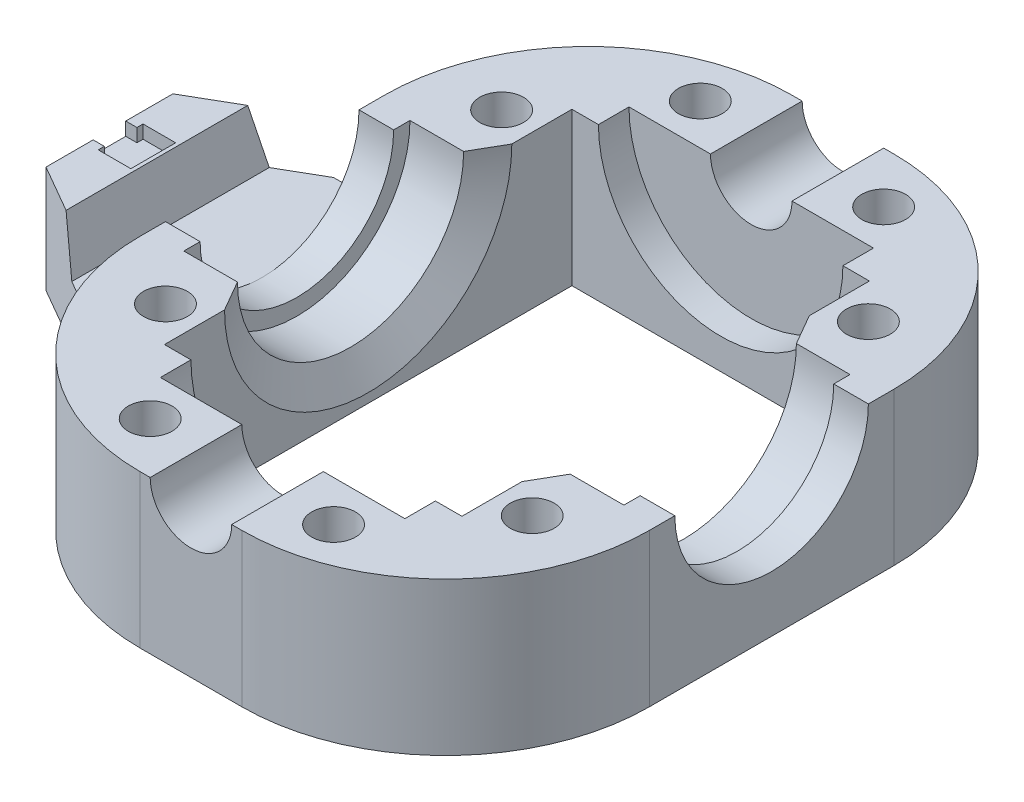
SolidWorks part; units mm, degrees
ref_plane "Спереди" through (0, 0, 0) normal (0, 0, 1) x (1, 0, 0)
ref_plane "Сверху" through (0, 0, 0) normal (0, 1, 0) x (1, 0, 0)
ref_plane "Справа" through (0, 0, 0) normal (1, 0, 0) x (0, 0, -1)
sketch "Sketch1" plane through (0, 0, 0) normal (0, 1, 0) x (1, 0, 0)
  line L1 (25, -32) -> (-25, -32)
  line L2 (25, -32) -> (25, 32)
  line L3 (25, 32) -> (-25, 32)
  line L4 (-25, -32) -> (-25, 32)
  line L5 (25, -32) -> (-25, 32) construction
  line L6 (25, 32) -> (-25, -32) construction
  line L7 (14.6, -20) -> (-14.6, -20)
  line L8 (14.6, -20) -> (14.6, 20)
  line L9 (14.6, 20) -> (-14.6, 20)
  line L10 (-14.6, -20) -> (-14.6, 20)
  line L11 (14.6, -20) -> (-14.6, 20) construction
  line L12 (14.6, 20) -> (-14.6, -20) construction
  point P0 (0, 0)
  point P6 (0, 0)
  dimension "D1" = 50
  dimension "D2" = 64
  dimension "D3" = 40
  dimension "D4" = 29.2
extrude "Boss-Extrude1" add sketch "Sketch1" along normal blind 15
sketch "Sketch3" plane through (0, 15, 0) normal (0, 1, 0) x (1, 0, 0)
  line L0 (-14.6, 0) -> (-25, 0) construction
  line L1 (-14.6, 20) -> (-14.6, -20) construction
  line L2 (-25, 32) -> (-25, -32) construction
  line L3 (14.6, 0) -> (25, 0) construction
  line L4 (14.6, -20) -> (14.6, 20) construction
  line L5 (25, -32) -> (25, 32) construction
  line L10 (14.6, -11.1) -> (21.6, -11.1)
  line L11 (14.6, -11.1) -> (14.6, 0)
  line L12 (14.6, 0) -> (21.6, 0)
  line L13 (21.6, -11.1) -> (21.6, 0)
  line L14 (14.6, -11.1) -> (21.6, 0) construction
  line L15 (14.6, 0) -> (21.6, -11.1) construction
  line L16 (-21.6, -11.1) -> (-14.6, -11.1)
  line L17 (-21.6, -11.1) -> (-21.6, 0)
  line L18 (-21.6, 0) -> (-14.6, 0)
  line L19 (-14.6, -11.1) -> (-14.6, 0)
  line L20 (-21.6, -11.1) -> (-14.6, 0) construction
  line L21 (-21.6, 0) -> (-14.6, -11.1) construction
  point P18 (18.1, -5.55)
  point P23 (-18.1, -5.55)
  dimension "D1" = 7
  dimension "D2" = 11.1
revolve "Cut-Revolve1" cut sketch "Sketch3" angle 360 about L12
sketch "Sketch4" plane through (25, 0, 0) normal (1, 0, 0) x (0, 0, -1)
  line L0 (-32, 15) -> (32, 15) construction
  circle A0 centre (0, 15) radius 9.5
  dimension "D1" = 19
extrude "Cut-Extrude2" cut sketch "Sketch4" against normal through all
sketch "Sketch5" plane through (0, 0, 32) normal (0, 0, 1) x (1, 0, 0)
  line L0 (-25, 15) -> (25, 15) construction
  circle A0 centre (0, 15) radius 4
  dimension "D1" = 8
extrude "Cut-Extrude3" cut sketch "Sketch5" against normal through all
sketch "Sketch8" plane through (0, 15, 0) normal (0, 1, 0) x (1, 0, 0)
  line L1 (-18, -16.5) -> (18, -16.5) construction
  line L2 (-18, -16.5) -> (-18, 16.5) construction
  line L3 (-18, 16.5) -> (18, 16.5) construction
  line L4 (18, -16.5) -> (18, 16.5) construction
  line L5 (-18, -16.5) -> (18, 16.5) construction
  line L6 (-18, 16.5) -> (18, -16.5) construction
  line L7 (-9, 27) -> (9, 27) construction
  line L8 (-9, 27) -> (-9, -27) construction
  line L9 (-9, -27) -> (9, -27) construction
  line L10 (9, 27) -> (9, -27) construction
  line L11 (-9, 27) -> (9, -27) construction
  line L12 (-9, -27) -> (9, 27) construction
  circle A0 centre (18, 16.5) radius 2.15
  circle A1 centre (18, -16.5) radius 2.15
  circle A2 centre (-18, -16.5) radius 2.15
  circle A3 centre (-18, 16.5) radius 2.15
  circle A4 centre (9, -27) radius 2.15
  circle A5 centre (-9, -27) radius 2.15
  circle A6 centre (-9, 27) radius 2.15
  circle A7 centre (9, 27) radius 2.15
  point P0 (0, 0)
  point P10 (0, 0)
  dimension "D3" = 4.3
  dimension "D1" = 33
  dimension "D2" = 36
  dimension "D4" = 18
  dimension "D5" = 54
extrude "Cut-Extrude6" cut sketch "Sketch8" against normal through all
fillet "Fillet1" radius 20 4 edges at (-25, 7.5, 32) (-25, 7.5, -32) (25, 7.5, -32) (25, 7.5, 32)
chamfer "Chamfer1" distance 3 angle 30 2 edges at (-14.6, 3.9, 0) (14.6, 3.9, 0) first distance on face at (-14.6, 8.15, 0) first distance on face at (14.6, 8.15, 0)
sketch "Sketch9" plane through (0, 15, 0) normal (0, 1, 0) x (1, 0, 0)
  line L0 (0, 29.8714) -> (0, -31.0419) construction
  line L1 (-4, 20) -> (-14.6, 20) construction
  line L2 (-12, -23) -> (0, -23)
  line L3 (-12, -23) -> (-12, -20)
  line L4 (-12, -20) -> (0, -20)
  line L5 (0, -23) -> (0, -20)
  line L6 (-12, -23) -> (0, -20) construction
  line L7 (-12, -20) -> (0, -23) construction
  line L8 (-12, 20) -> (0, 20)
  line L9 (-12, 20) -> (-12, 23)
  line L10 (-12, 23) -> (0, 23)
  line L11 (0, 20) -> (0, 23)
  line L12 (-12, 20) -> (0, 23) construction
  line L13 (-12, 23) -> (0, 20) construction
  line L14 (-14.6, -20) -> (-4, -20) construction
  point P3 (-6, -21.5)
  point P8 (-6, 21.5)
  dimension "D1" = 3
  dimension "D2" = 12
revolve "Cut-Revolve2" cut sketch "Sketch9" angle 360 about L0
sketch "Sketch10" plane through (-25, 0, 0) normal (-1, 0, 0) x (0, 0, 1)
  line L0 (-9.5, 15) -> (9.5, 15) construction
  line L1 (0, 15) -> (0, 0) construction
  line L2 (-12, 0) -> (12, 0) construction
  line L4 (12, 5.5) -> (-12, 5.5)
  line L5 (12, 5.5) -> (12, 0)
  line L6 (12, 0) -> (-12, 0)
  line L7 (-12, 5.5) -> (-12, 0)
  line L8 (12, 5.5) -> (-12, 0) construction
  line L9 (12, 0) -> (-12, 5.5) construction
  arc A0 (-9.5, 15) -> (9.5, 15) centre (0, 15) ccw construction
  point P8 (0, 2.75)
extrude "Boss-Extrude2" add sketch "Sketch10" along normal blind 15
sketch "Sketch12" plane through (-25, 0, 0) normal (-1, 0, 0) x (0, 0, 1)
  line L0 (-9.5, 15) -> (9.5, 15) construction
  line L1 (0, 15) -> (0, 0) construction
  line L3 (12, 9.2) -> (-12, 9.2)
  line L4 (12, 9.2) -> (12, 5.5)
  line L5 (12, 5.5) -> (-12, 5.5)
  line L6 (-12, 9.2) -> (-12, 5.5)
  line L7 (12, 9.2) -> (-12, 5.5) construction
  line L8 (12, 5.5) -> (-12, 9.2) construction
  point P7 (0, 7.35)
  dimension "D1" = 5.8
extrude "Boss-Extrude3" add sketch "Sketch12" along normal up to surface (15 mm away) from offset 9 up to face at (-40, 2.75, 0)
sketch "Sketch13" plane through (0, 9.2, 0) normal (0, 1, 0) x (1, 0, 0)
  line L0 (-34, 0) -> (-40, 0) construction
  line L1 (-34, -12) -> (-34, 12) construction
  line L2 (-40, 12) -> (-40, -12) construction
  line L3 (-38.9, 2.2) -> (-38.9, 1.6)
  line L4 (-38.9, -2.2) -> (-35.7, -2.2)
  line L5 (-38.9, 1.6) -> (-40, 1.6)
  line L6 (-38.9, 2.2) -> (-35.7, 2.2)
  line L7 (-35.7, -2.2) -> (-35.7, 2.2)
  line L8 (-38.9, -2.2) -> (-35.7, 2.2) construction
  line L9 (-38.9, 2.2) -> (-35.7, -2.2) construction
  line L10 (-38.9, -2.2) -> (-38.9, -1.6)
  line L11 (-38.9, -1.6) -> (-40, -1.6)
  line L12 (-40, -1.6) -> (-40, -12)
  line L13 (-40, -12) -> (-34, -12)
  line L14 (-34, -12) -> (-34, 12)
  line L15 (-34, 12) -> (-40, 12)
  line L16 (-40, 12) -> (-40, 1.6)
  point P6 (-37.3, 0)
  dimension "D1" = 3.2
  dimension "D2" = 4.4
  dimension "D3" = 3.2
  dimension "D4" = 2.7
extrude "Boss-Extrude4" add sketch "Sketch13" along normal blind 1.3
chamfer "Chamfer2" distance 5 angle 15 1 edges at (-34, 10.5, 0) first distance on face at (-34, 8, 0)
chamfer "Chamfer3" distance 10 angle 30 2 edges at (-40, 5.25, 12) (-40, 5.25, -12) first distance on face at (-33.2233, 5.3333, 12) first distance on face at (-33.2233, 5.3333, -12)
